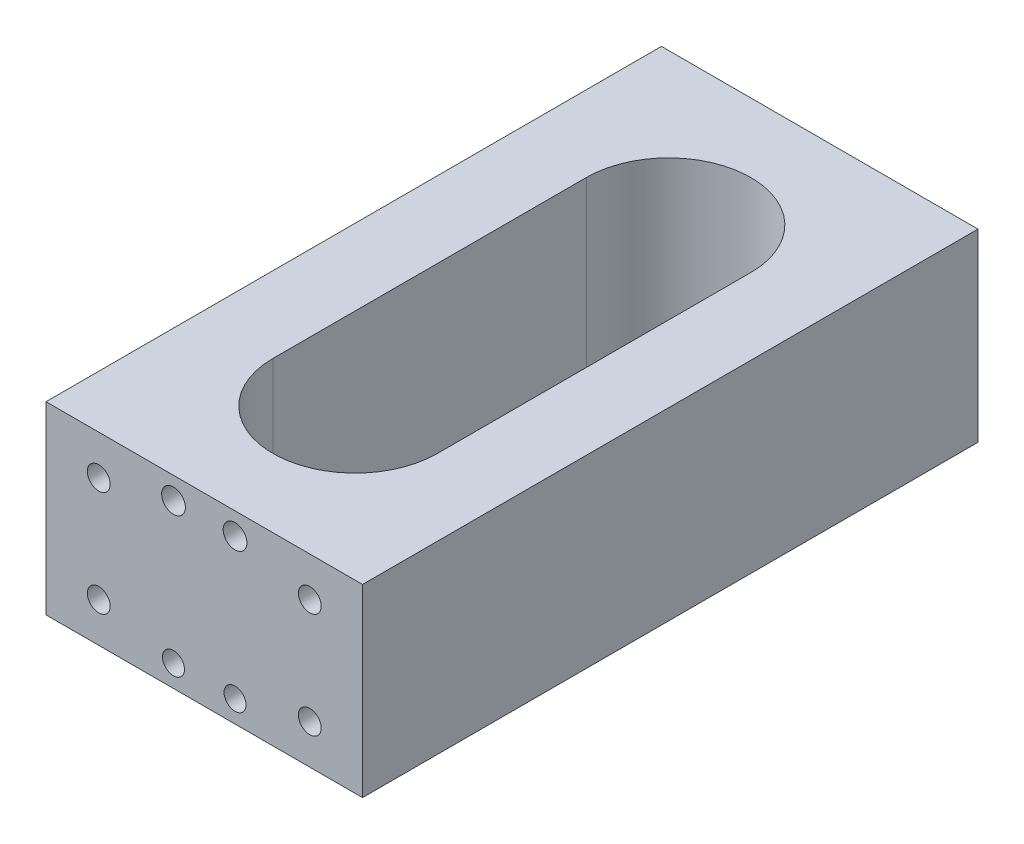
SolidWorks part; units mm, degrees
ref_plane "정면" through (0, 0, 0) normal (0, 0, 1) x (1, 0, 0)
ref_plane "윗면" through (0, 0, 0) normal (0, 1, 0) x (1, 0, 0)
ref_plane "우측면" through (0, 0, 0) normal (1, 0, 0) x (0, 0, -1)
sketch "스케치1" plane through (0, 0, 0) normal (0, 0, 1) x (1, 0, 0)
  line L0 (0, 10.5) -> (0, -10.5) construction
  line L1 (18, -10.5) -> (-18, -10.5)
  line L2 (18, -10.5) -> (18, 10.5)
  line L3 (18, 10.5) -> (-18, 10.5)
  line L4 (-18, -10.5) -> (-18, 10.5)
  line L5 (18, -10.5) -> (-18, 10.5) construction
  line L6 (18, 10.5) -> (-18, -10.5) construction
  line L7 (18, 0) -> (-18, 0) construction
  circle A0 centre (12, 6) radius 1.3
  circle A1 centre (-12, 6) radius 1.3
  circle A2 centre (12, -6) radius 1.3
  circle A3 centre (-12, -6) radius 1.3
  circle A4 centre (3.5, -8) radius 1.25
  circle A5 centre (-3.5, -8) radius 1.25
  circle A6 centre (3.5, 8) radius 1.35
  circle A7 centre (-3.5, 8) radius 1.35
  point P1 (0, 0)
extrude "보스-돌출1" add sketch "스케치1" along normal blind 70 contours A0 | A6 | A7 | A1 | A3 | A5 | A4 | A2 | L4 L1 L2 L3 A5 A4 A1 A0 A2 A3 A6 A7 region at (0, -0.0183, 0) region at (12, 6, 0) region at (-12, 6, 0) region at (12, -6, 0) region at (-12, -6, 0) region at (3.5, -8, 0) region at (-3.5, -8, 0) region at (3.5, 8, 0) region at (-3.5, 8, 0)
extrude "컷-돌출1" cut sketch "스케치1<5>" along normal blind 4 contours A0 | A6 | A7 | A1 | A3 | A5 | A4 | A2 region at (12, 6, 0) region at (-12, 6, 0) region at (-12, -6, 0) region at (3.5, 8, 0) region at (-3.5, 8, 0)
sketch "스케치1<5>" plane through (0, 0, 0) normal (0, 0, 1) x (1, 0, 0) same geometry as "스케치1"
extrude "컷-돌출2" cut sketch "스케치1<6>" against normal blind 4 from surface contours A6 | A0 | A7 | A1 | A3 | A5 | A4 | A2 region at (12, 6, 0) region at (-12, 6, 0) region at (12, -6, 0) region at (-12, -6, 0) region at (3.5, -8, 0) region at (-3.5, -8, 0) region at (3.5, 8, 0) region at (-3.5, 8, 0) starting at face at (0, 0, 70)
sketch "스케치1<6>" plane through (0, 0, 0) normal (0, 0, 1) x (1, 0, 0) same geometry as "스케치1"
sketch "Sketch1" plane through (0, 10.5, 0) normal (0, 1, 0) x (1, 0, 0)
  line L0 (0, -17.1933) -> (0, -52.8417) construction
  line L1 (9.3571, -17.1933) -> (9.3571, -52.8417)
  line L2 (-9.3571, -17.1933) -> (-9.3571, -52.8417)
  arc A0 (9.3571, -17.1933) -> (-9.3571, -17.1933) centre (0, -17.1933) ccw
  arc A1 (-9.3571, -52.8417) -> (9.3571, -52.8417) centre (0, -52.8417) ccw
  point P3 (0, -35.0175)
extrude "Cut-Extrude1" cut sketch "Sketch1" against normal blind 30
